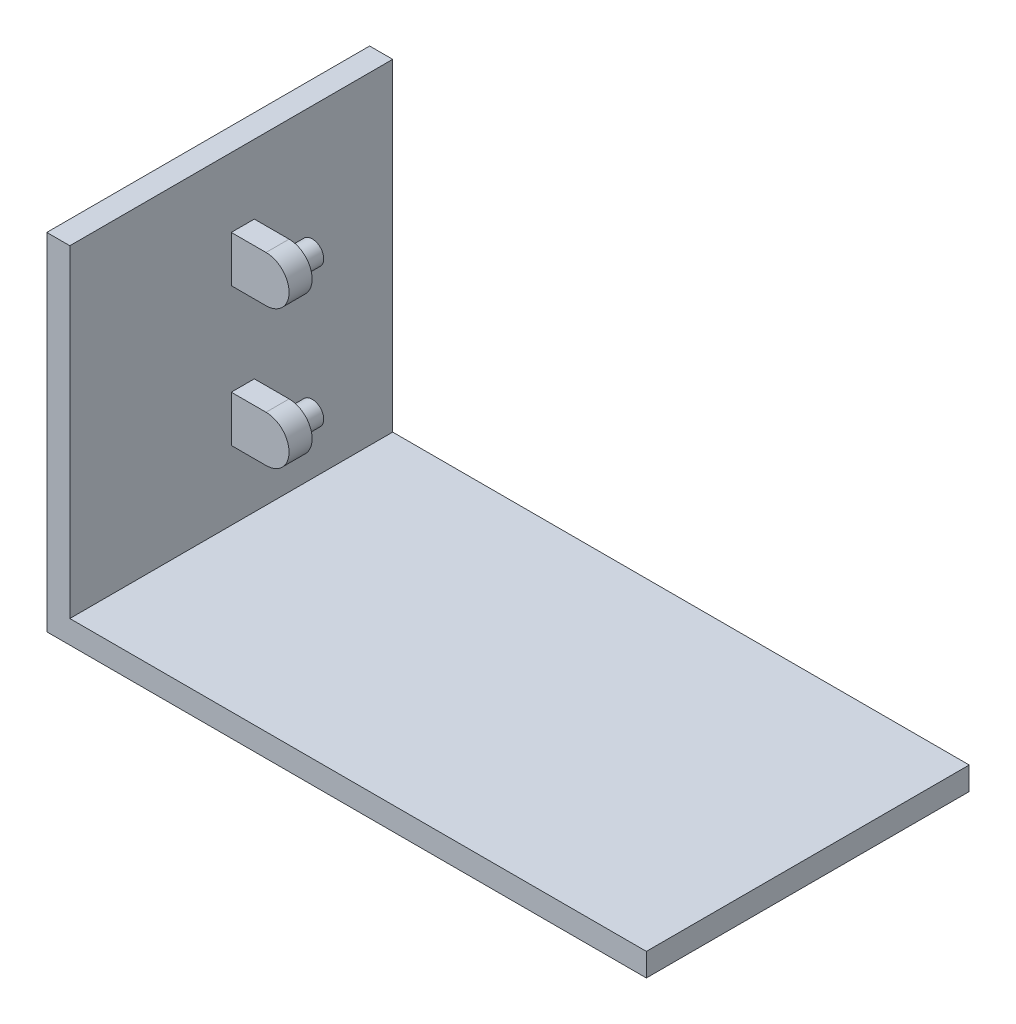
SolidWorks part; units mm, degrees
ref_plane "Piano frontale" through (0, 0, 0) normal (0, 0, 1) x (1, 0, 0)
ref_plane "Piano superiore" through (0, 0, 0) normal (0, 1, 0) x (1, 0, 0)
ref_plane "Piano destro" through (0, 0, 0) normal (1, 0, 0) x (0, 0, -1)
sketch "Schizzo1" plane through (0, 0, 0) normal (0, 0, 1) x (1, 0, 0)
  line L1 (0, 0) -> (-5, 0)
  line L2 (0, 0) -> (0, 70)
  line L3 (0, 70) -> (-5, 70)
  line L4 (-5, 0) -> (-5, 70)
  dimension "D1" = 70
  dimension "D2" = 5
extrude "Estrusione-Estrusione1" add sketch "Schizzo1" along normal blind 70
sketch "Schizzo2" plane through (0, 0, 70) normal (0, 0, 1) x (1, 0, 0)
  line L0 (0, 15) -> (0, 20)
  line L1 (0, 0) -> (0, 70) construction
  line L2 (0, 45) -> (0, 50)
  line L3 (7.5316, 55) -> (0, 55)
  line L4 (0, 55) -> (0, 45)
  line L5 (0, 45) -> (7.5316, 45)
  line L6 (7.5316, 25) -> (0, 25)
  line L7 (0, 25) -> (0, 15)
  line L8 (0, 15) -> (7.5316, 15)
  arc A0 (7.5316, 45) -> (7.5316, 55) centre (7.5316, 50) ccw
  arc A1 (7.5316, 15) -> (7.5316, 25) centre (7.5316, 20) ccw
  line M1 (0, 0) -> (0, 70)
  dimension "D1" = 10
  dimension "D2" = 10
extrude "Estrusione-Estrusione2" add sketch "Schizzo2" against normal blind 5 from offset 35 contours L5 A0 L3 M1 | L8 A1 L6 M1 region at (5.7836, 50, 70) region at (5.7836, 20, 70) offset against normal yes
sketch "Schizzo3" plane through (0, 0, 30) normal (0, 0, -1) x (-1, 0, 0)
  circle A0 centre (-7.5476, 50.0613) radius 2.5
  circle A1 centre (-7.5476, 19.9398) radius 2.5
  point P2 (-7.5476, 50.0613)
  point P4 (-7.5476, 19.9398)
  point P7 (-7.9573, 19.9398)
  dimension "D1" = 5
  dimension "D2" = 5
extrude "Estrusione-Estrusione3" add sketch "Schizzo3" along normal blind 5
sketch "Schizzo4" plane through (0, 0, 0) normal (0, -1, 0) x (1, 0, 0)
  line L1 (-5, 0) -> (125, 0)
  line L2 (-5, 0) -> (-5, 70)
  line L3 (-5, 70) -> (125, 70)
  line L4 (125, 0) -> (125, 70)
extrude "Estrusione-Estrusione4" add sketch "Schizzo4" along normal blind 5
